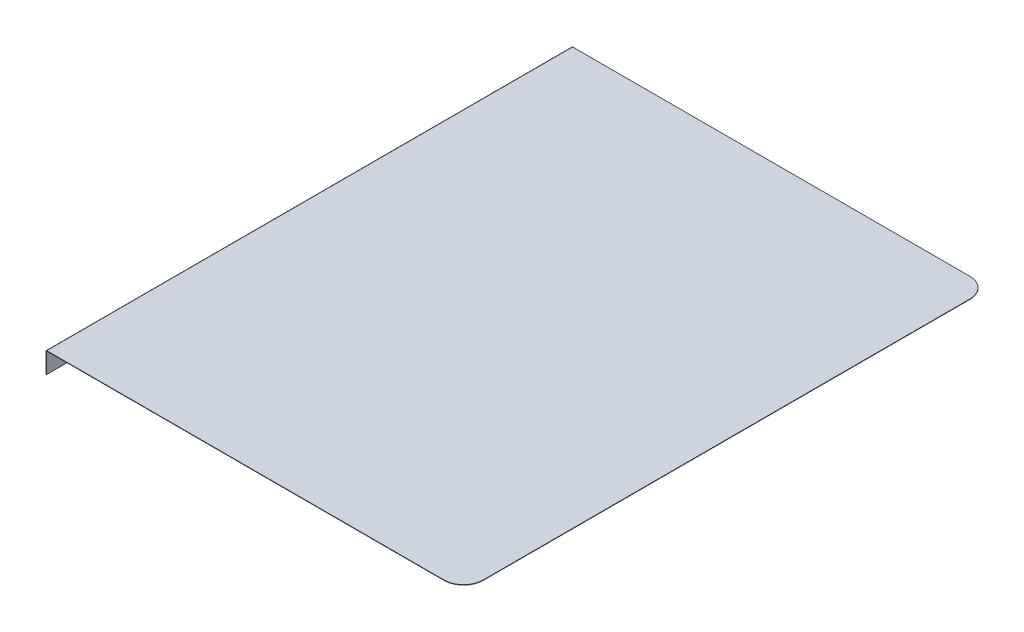
SolidWorks part; units mm, degrees
note: The reader was unsure of these and kept them because the rebuilt part matched: flange length of "Edge-Flange1".
material "AISI 1020 Steel, Cold Rolled"
ref_plane "Front Plane" through (0, 0, 0) normal (0, 0, 1) x (1, 0, 0)
ref_plane "Top Plane" through (0, 0, 0) normal (0, 1, 0) x (1, 0, 0)
ref_plane "Right Plane" through (0, 0, 0) normal (1, 0, 0) x (0, 0, -1)
sketch "Sketch1" plane through (0, 0, 0) normal (0, 1, 0) x (1, 0, 0)
  line L1 (-405, 510) -> (405, 510)
  line L2 (-405, 510) -> (-405, -510)
  line L3 (-405, -510) -> (405, -510)
  line L4 (405, 510) -> (405, -510)
  line L5 (-405, 510) -> (405, -510) construction
  line L6 (-405, -510) -> (405, 510) construction
  point P0 (0, 0)
  dimension "D1" = 1020
  dimension "D2" = 810
sheet metal parameters "Sheet-Metal1" thickness 0.8 parameters "D1"=1.2
base flange "Base-Flange1" sketch "Sketch1" thickness 0.8 reverse thickness direction no parameters "D1"=1.2
sketch "Sketch3" plane through (0, 0, 0) normal (0, 1, 0) x (1, 0, 0)
  line L0 (364.2, 510) -> (405, 469.2)
  line L1 (405, 510) -> (364.2, 510)
  line L2 (405, 510) -> (405, 469.2)
  dimension "D1" = 40.8
  dimension "D2" = 40.8
edge flange "Edge-Flange1" sketch "Sketch6" flange angle 90 flange length 40.8 flange position material inside bend radius 0.8 thickness 0.8 parameters "D6"=10
sketch "Sketch6" plane through (-405, -0.8, 0) normal (1, 0, 0) x (0, 0, 1)
  line L1 (510, 0) -> (-510, 0) construction
  line L2 (-510, 0) -> (-510, 40)
  line L3 (-510, 40) -> (510, 40)
  line L4 (510, 40) -> (510, 0)
  line L5 (510, 0) -> (-510, 0)
bend "EdgeBend1" bend radius 0.8 bend angle 90 parameters "D5"=1
sketch "Sketch7" plane through (0, 0, 0) normal (0, 1, 0) x (1, 0, 0)
  line L0 (405, 510) -> (367, 510)
  line L1 (405, 510) -> (-403.4, 510) construction
  line L2 (405, 510) -> (405, 472)
  line L3 (405, -510) -> (405, 510) construction
  line L4 (405, -510) -> (367, -510)
  line L5 (-403.4, -510) -> (405, -510) construction
  line L6 (405, -510) -> (405, -472)
  arc A0 (405, 472) -> (367, 510) centre (367, 472) ccw
  arc A1 (367, -510) -> (405, -472) centre (367, -472) ccw
  dimension "D1" = 38
  dimension "D2" = 38
  dimension "D3" = 38
  dimension "D4" = 38
extrude "Cut-Extrude2" cut sketch "Sketch7" against normal blind 10 normal cut yes
flat pattern "Flat-Pattern1" [suppressed]
sketch "Bend-Lines1" plane through (0, 0, 0) normal (0, 1, 0) x (-1, 0, 0)
  line L0 (473.1111, -638.8) -> (473.1111, 638.8) construction
  line L1 (473.1111, -638.8) -> (473.1111, 638.8) construction
bend of the flat pattern "Flatten-<EdgeBend1>1"
